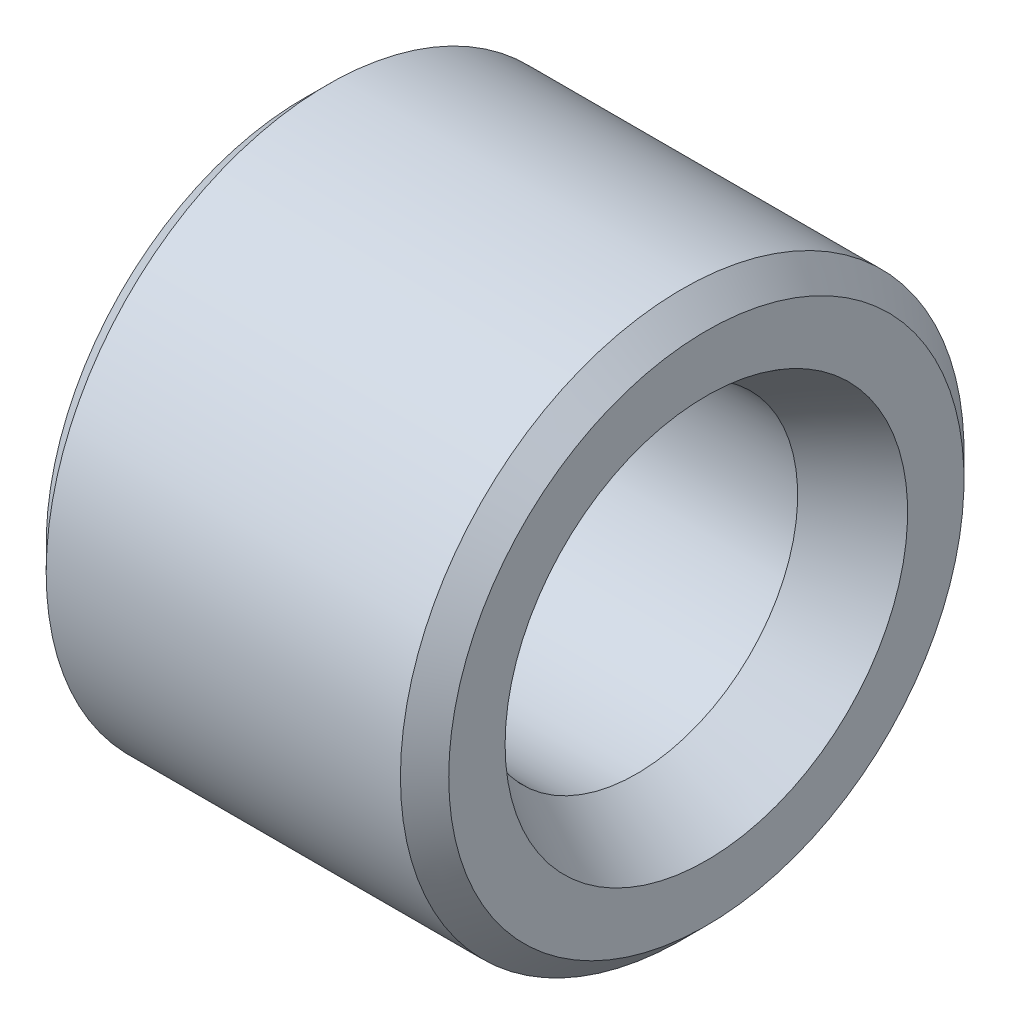
SolidWorks part; units mm, degrees
ref_plane "Front Plane" through (0, 0, 0) normal (0, 0, 1) x (1, 0, 0)
ref_plane "Top Plane" through (0, 0, 0) normal (0, 1, 0) x (1, 0, 0)
ref_plane "Right Plane" through (0, 0, 0) normal (1, 0, 0) x (0, 0, -1)
sketch "Sketch1" plane through (0, 0, 0) normal (0, 0, 1) x (1, 0, 0)
  line L0 (0, 0) -> (5, 0) construction
  line L1 (0, 2) -> (0, 3.5)
  line L2 (0, 3.5) -> (5, 3.5)
  line L4 (5, 3.5) -> (5, 2)
  line L6 (5, 2) -> (0, 2)
  dimension "L" = 5
  dimension "D_s" = 4
  dimension "D" = 7
  dimension "T" = 1.5
revolve "Revolve1" add sketch "Sketch1" angle 360 about L0
chamfer "Chamfer1" distance 0.3 angle 45 2 edges at (5, 0, 3.5) (0, 0, 3.5)
sketch "Sketch2" plane through (0, 0, 0) normal (0, 0, 1) x (1, 0, 0)
  line L0 (0, 0) -> (5, 0) construction
  line L1 (0, 2.5) -> (0, 2)
  line L2 (0, 2) -> (0.866, 2)
  line L3 (0.866, 2) -> (0, 2.5)
  line L4 (4.134, 2) -> (5, 2.5)
  line L5 (0, 2) -> (0, 3.5) construction
  line L8 (5, 2) -> (4.134, 2)
  line L9 (5, 2.5) -> (5, 2)
  line L10 (5, 2) -> (0, 2) construction
  line L11 (5, 3.5) -> (5, 2) construction
  dimension "FIX_4" = 0.5
  dimension "FIX_5" = 30
revolve "Cut-Revolve1" cut sketch "Sketch2" angle 360 about L0
